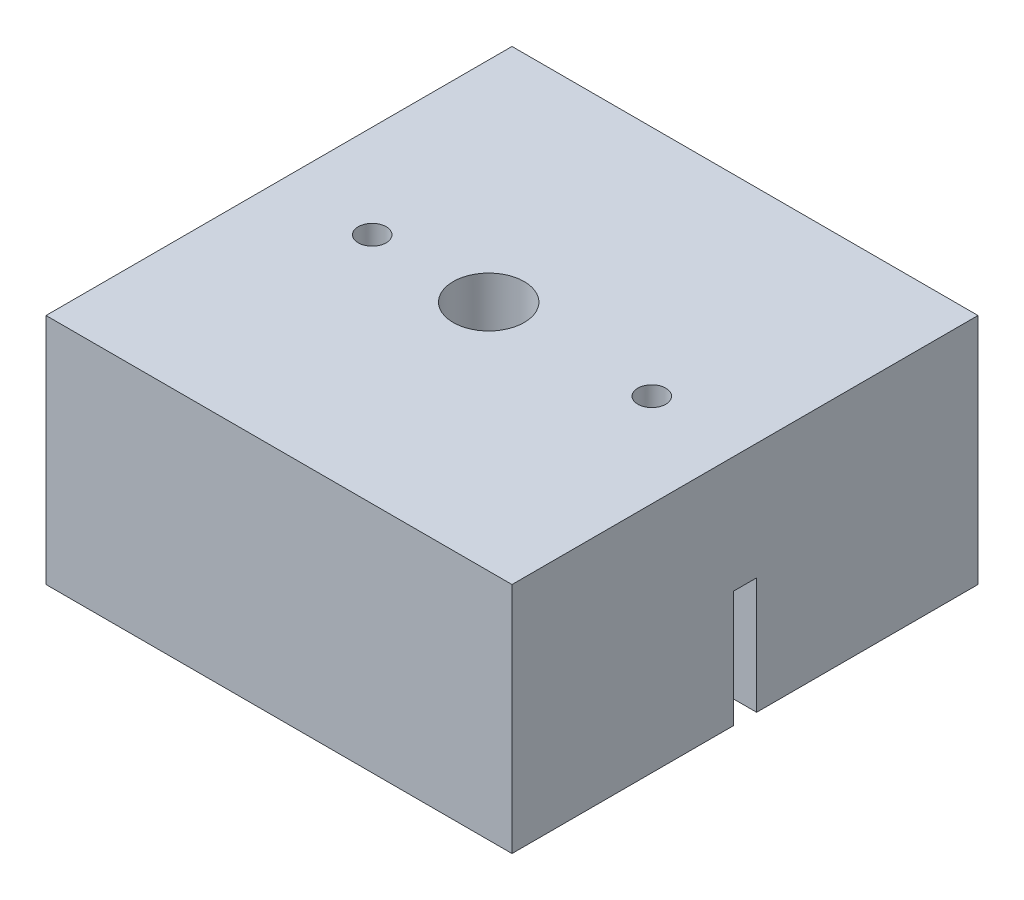
SolidWorks part; units mm, degrees
ref_plane "Front Plane" through (0, 0, 0) normal (0, 0, 1) x (1, 0, 0)
ref_plane "Top Plane" through (0, 0, 0) normal (0, 1, 0) x (1, 0, 0)
ref_plane "Right Plane" through (0, 0, 0) normal (1, 0, 0) x (0, 0, -1)
sketch "BaseWith Alignment" plane through (0, 0, 0) normal (0, 1, 0) x (1, 0, 0)
  line L0 (0, 5) -> (0, -5) construction
  line L1 (-5, 5) -> (5, 5)
  line L2 (-5, 5) -> (-5, -5)
  line L3 (-5, -5) -> (5, -5)
  line L4 (5, 5) -> (5, -5)
  dimension "D1" = 10
  dimension "D2" = 10
extrude "Boss-Extrude1" add sketch "BaseWith Alignment" along normal blind 5
sketch "Sketch1" plane through (0, 0, 0) normal (0, -1, 0) x (-1, 0, 0)
  line L0 (-3, 0) -> (3, 0) construction
  line L1 (-3, 1.25) -> (3, 1.25) construction
  line L2 (-3, -1.25) -> (3, -1.25) construction
  line L22 (0.5, 0) -> (0.3393, 1.2396) construction
  line L23 (2.0179, 1.9614) -> (2.0179, -1.9614) construction
  line L25 (2.0179, -1.9614) -> (-3.1107, -1.2965)
  line L27 (2.0179, 1.9614) -> (-3.1107, 1.2965)
  line L28 (-3.1107, 1.2965) -> (-3.1107, -1.2965) construction
  line L29 (-3, 0) -> (-3.0386, 0.2975) construction
  line L30 (0.3393, 1.2396) -> (0.275, 1.7355) construction
  line L31 (-3.0386, 0.2975) -> (-3.1671, 1.2892) construction
  arc A0 (-3, 1.25) -> (-3, -1.25) centre (-3, 0) ccw construction
  arc A1 (3, -1.25) -> (3, 1.25) centre (3, 0) ccw construction
  circle A2 centre (0.5, 0) radius 0.762
  circle A3 centre (3, 0) radius 0.3
  circle A4 centre (-3, 0) radius 0.3
  arc A7 (-3.1, 0.2828) -> (-2.7, 0) centre (-3, 0) ccw construction
  circle A8 centre (0.5, 0) radius 1.25 construction
  circle A9 centre (0.5, 0) radius 1 construction
  arc A12 (2.0179, 1.9614) -> (2.0179, -1.9614) centre (2.2722, 0) cw
  arc A13 (-3.1107, 1.2965) -> (-3.1107, -1.2965) centre (-2.9426, 0) ccw
  point P2 (0, 0)
  point P25 (2.0179, 0)
  point P29 (-3.0543, 0)
  point P31 (-3.1107, 0)
  dimension "D3" = 0.6
  dimension "D5" = 1.524
  dimension "D6" = 0.6
  dimension "D7" = 2.5
  dimension "D8" = 2
  dimension "D2" = 2.5
  dimension "D4" = 2.5
  dimension "D1" = 3.5
  dimension "D10" = 3.9229
  dimension "D9" = 0.5
  dimension "D11" = 1
extrude "Cut-Extrude6" cut sketch "Sketch1" against normal through all contours A4 | A2 | A3
extrude "Cut-Extrude7" cut sketch "Sketch1<3>" against normal blind 2.5 contours L25 A13 L27 A12
sketch "Sketch1<3>" plane through (0, 0, 0) normal (0, -1, 0) x (-1, 0, 0) same geometry as "Sketch1"
sketch "Sketch2" plane through (0, 0, 0) normal (0, -1, 0) x (1, 0, 0)
  line L0 (-5, 0) -> (5, 0) construction
  line L1 (-5, -5) -> (-5, 5) construction
  line L2 (5, 5) -> (5, -5) construction
  line L4 (-5, 0.25) -> (5, 0.25)
  line L5 (5, 0.25) -> (5, -0.25)
  line L6 (5, -0.25) -> (-5, -0.25)
  line L7 (-5, -0.25) -> (-5, 0.25)
  point P8 (0, 0)
  dimension "D1" = 0.5
extrude "Cut-Extrude8" cut sketch "Sketch2" against normal up to surface (2.5 mm away) up to face at (-0.5, 2.5, 0.762)
equation "\"StabilizerRodeHole\"=0.6"
equation "\"D3@Sketch1\"=\"StabilizerRodeHole\""
equation "\"D6@Sketch1\"=\"StabilizerRodeHole\""
